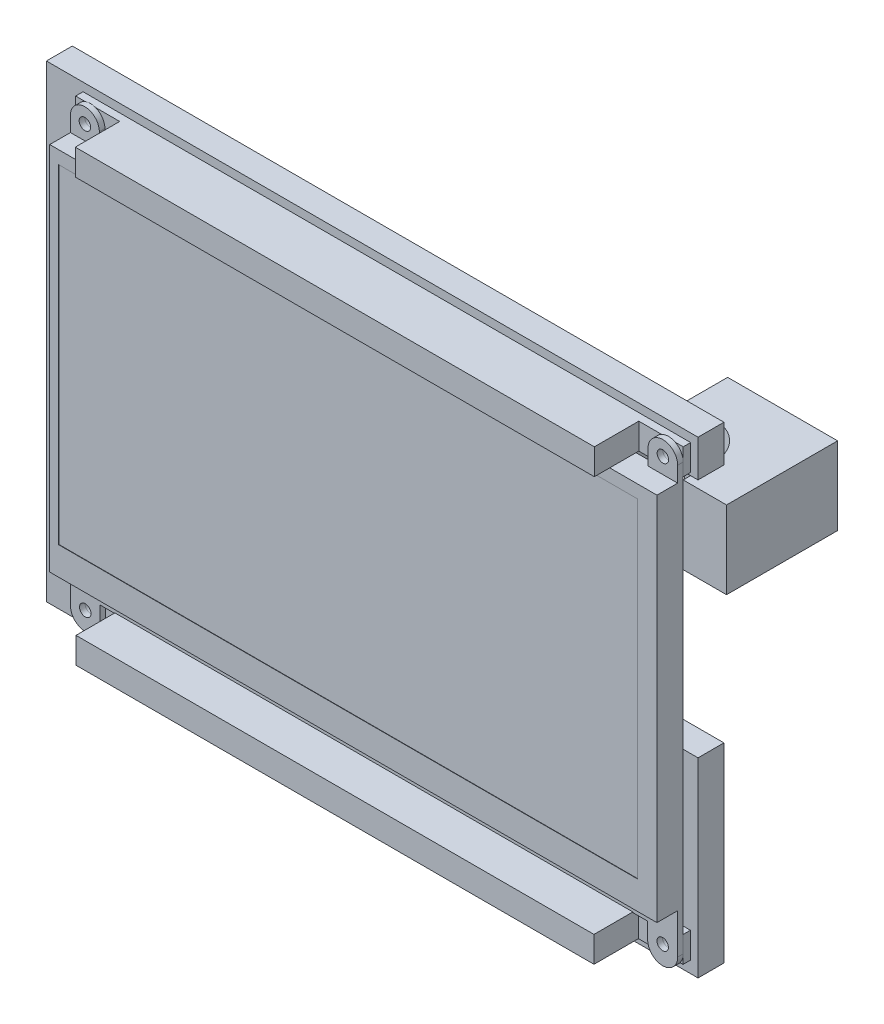
SolidWorks part; units mm, degrees
material "PVC Rigid"
ref_plane "Front Plane" through (0, 0, 0) normal (0, 0, 1) x (1, 0, 0)
ref_plane "Top Plane" through (0, 0, 0) normal (0, 1, 0) x (1, 0, 0)
ref_plane "Right Plane" through (0, 0, 0) normal (1, 0, 0) x (0, 0, -1)
sketch "Sketch1" plane through (0, 0, 0) normal (0, 0, 1) x (1, 0, 0)
  line L1 (-82, -53.25) -> (82, -53.25)
  line L2 (-82, -53.25) -> (-82, 53.25)
  line L3 (-82, 53.25) -> (82, 53.25)
  line L4 (82, -53.25) -> (82, 53.25)
  line L5 (-82, -53.25) -> (82, 53.25) construction
  line L6 (-82, 53.25) -> (82, -53.25) construction
  line L7 (-82, 53.25) -> (-74.2, 53.25)
  line L8 (-82, 53.25) -> (-82, 57.35)
  line L10 (-74.2, 53.25) -> (-74.2, 57.35)
  line L11 (82, 53.25) -> (74, 53.25)
  line L12 (82, 53.25) -> (82, 57.45)
  line L14 (74, 53.25) -> (74, 57.45)
  line L15 (-82, -53.25) -> (-74, -53.25)
  line L16 (-82, -53.25) -> (-82, -57.45)
  line L18 (-74, -53.25) -> (-74, -57.45)
  line L19 (82, -53.25) -> (73.9, -53.25)
  line L20 (82, -53.25) -> (82, -57.6)
  line L22 (73.9, -53.25) -> (73.9, -57.6)
  arc A0 (-74.2, 57.35) -> (-82, 57.35) centre (-78.1, 57.35) ccw
  arc A1 (82, 57.45) -> (74, 57.45) centre (78, 57.45) ccw
  arc A2 (-74, -57.45) -> (-82, -57.45) centre (-78, -57.45) cw
  arc A3 (82, -57.6) -> (73.9, -57.6) centre (77.95, -57.6) cw
  circle A4 centre (77.95, -56.6) radius 1.55
  circle A5 centre (-78, -56.5) radius 1.55
  circle A6 centre (-78.1, 57.2) radius 1.55
  circle A7 centre (78, 57.5) radius 1.55
  point P0 (0, 0)
  point P14 (78, 61.45)
  point P15 (-78.1, 61.25)
  point P24 (-78, -61.45)
  point P25 (77.95, -61.65)
  point P26 (77.1665, -53.25)
  point P29 (77.95, -58.15)
  point P32 (-78.1, 58.75)
  point P37 (-78, -58.05)
  point P38 (78, 59.05)
  dimension "D15" = 3.1
  dimension "D1" = 106.5
  dimension "D2" = 164
  dimension "D3" = 7.8
  dimension "D4" = 8
  dimension "D5" = 8.2
  dimension "D6" = 8
  dimension "D7" = 8.2
  dimension "D8" = 8.4
  dimension "D9" = 3.5
  dimension "D10" = 8.1
  dimension "D11" = 8
  dimension "D12" = 3.4
  dimension "D13" = 2.5
  dimension "D14" = 2.4
extrude "Boss-Extrude1" add sketch "Sketch1" along normal blind 1.5 contours L1 L4 L3 L2 | A2 L18 L1 L16 A5 | A3 L20 L1 L22 A4 | L10 A0 L8 L3 A6 | L12 A1 L14 L3 A7 region at (0, 0, 0) region at (-78, -53.3646, 0) region at (-81.8883, 55.3, 0) region at (77.95, -53.3667, 0) region at (74.1146, 55.35, 0)
sketch "Sketch3" plane through (0, 0, 1.5) normal (0, 0, 1) x (1, 0, 0)
  line L0 (-82, -57.45) -> (-82, 57.35) construction
  line L1 (-82, 53.25) -> (82, 53.25)
  line L2 (-82, 53.25) -> (-82, -46.75)
  line L3 (-82, -46.75) -> (82, -46.75)
  line L4 (82, 53.25) -> (82, -46.75)
  line L5 (82, -57.6) -> (82, 57.45) construction
  line L6 (-74.2, 53.25) -> (74, 53.25) construction
  line L8 (-79.6, 49.75) -> (76.8, 49.75)
  line L9 (-79.6, 49.75) -> (-79.6, -39.15)
  line L10 (-79.6, -39.15) -> (76.8, -39.15)
  line L11 (76.8, 49.75) -> (76.8, -39.15)
  dimension "D1" = 100
  dimension "D2" = 3.5
  dimension "D3" = 2.4
  dimension "D4" = 5.2
  dimension "D5" = 7.6
extrude "Boss-Extrude2" add sketch "Sketch3" along normal blind 7.1 from surface starting at face at (-0.05, -0.0542, 0)
extrude "Boss-Extrude3" add sketch "Sketch3<2>" along normal blind 7 from surface contours L11 L8 L9 L10 region at (-1.4, 5.3, 1.5) starting at face at (-0.05, -0.0542, 0)
sketch "Sketch3<2>" plane through (0, 0, 1.5) normal (0, 0, 1) x (1, 0, 0) same geometry as "Sketch3"
sketch "Sketch4" plane through (0, 0, 0) normal (0, 0, -1) x (-1, 0, 0)
  line L0 (82, -57.45) -> (82, 57.35) construction
  line L1 (-82, 53.25) -> (82, 53.25)
  line L2 (-82, 53.25) -> (-82, -11.75)
  line L3 (-82, -11.75) -> (82, -11.75)
  line L4 (82, 53.25) -> (82, -11.75)
  dimension "D1" = 65
extrude "Boss-Extrude4" add sketch "Sketch4" along normal blind 6
sketch "Sketch5" plane through (0, 0, 0) normal (0, 0, -1) x (-1, 0, 0)
  line L0 (-82, 53.25) -> (-82, -11.75) construction
  line L1 (-82, 53.25) -> (-93.7, 53.25)
  line L2 (-82, 53.25) -> (-82, 32.25)
  line L3 (-82, 32.25) -> (-93.7, 32.25)
  line L4 (-93.7, 53.25) -> (-93.7, 32.25)
  dimension "D1" = 11.7
  dimension "D2" = 21
extrude "Boss-Extrude5" add sketch "Sketch5" along normal blind 30
sketch "Sketch6" plane through (82, 0, 0) normal (-1, 0, 0) x (0, 0, 1)
  line L1 (-30, 53.25) -> (-18.4, 53.25)
  line L2 (-30, 53.25) -> (-30, 32.25)
  line L3 (-30, 32.25) -> (-18.4, 32.25)
  line L4 (-18.4, 53.25) -> (-18.4, 32.25)
  line L6 (0, 53.25) -> (0, 57.35) construction
  line L7 (-30, 32.25) -> (-6, 32.25) construction
  dimension "D1" = 18.4
extrude "Boss-Extrude6" add sketch "Sketch6" along normal blind 18
fillet "Fillet1" radius 10 1 edges at (82, 42.75, -18.4)
sketch "Sketch7" plane through (0, 0, 0) normal (0, 0, -1) x (-1, 0, 0)
  line L0 (82, 53.25) -> (-82, 53.25) construction
  line L1 (-84, 63.25) -> (92, 63.25)
  line L2 (-84, 63.25) -> (-84, 53.25)
  line L3 (-57, 43.25) -> (72, 43.25)
  line L4 (92, 63.25) -> (92, 18.2824)
  line L6 (92, 18.2824) -> (92, -63.25)
  line L8 (72, 43.25) -> (72, -35.25)
  line L9 (92, -63.25) -> (-84, -63.25)
  line L11 (72, -35.25) -> (-72, -35.25)
  line L12 (-84, -63.25) -> (-84, -39.9785)
  line L14 (-84, -39.9785) -> (-84, -11.75)
  line L16 (-72, -35.25) -> (-72, -21.75)
  line L17 (74, -53.25) -> (-73.9, -53.25) construction
  line L18 (82, -11.75) -> (82, 53.25) construction
  line L19 (-82, 32.25) -> (-82, -11.75) construction
  line L20 (-76.8, 49.75) -> (79.6, 49.75) construction
  line L21 (-67, 53.25) -> (-84, 53.25)
  line L22 (-67, 53.25) -> (-67, -11.75)
  line L23 (-67, -11.75) -> (-84, -11.75)
  line L29 (-72, -21.75) -> (-57, -21.75)
  line L30 (-57, 43.25) -> (-57, -21.75)
  line L36 (-76.8, 49.75) -> (79.6, 49.75) construction
  line L37 (-6.1, -42.75) -> (8.9, -42.75) construction
  line L38 (-9.1, -42.75) -> (-6.1, -42.75)
  line L39 (-9.1, -42.75) -> (-9.1, -55.75)
  line L40 (-9.1, -55.75) -> (-6.1, -55.75)
  line L41 (-6.1, -42.75) -> (-6.1, -55.75)
  line L42 (8.9, -42.75) -> (11.9, -42.75)
  line L43 (8.9, -42.75) -> (8.9, -55.75)
  line L44 (8.9, -55.75) -> (11.9, -55.75)
  line L45 (11.9, -42.75) -> (11.9, -55.75)
  line L46 (-82, -57.6) -> (-82, -11.75) construction
  circle A0 centre (78.1, 57.2) radius 1.55 construction
  circle A1 centre (78, -56.5) radius 1.55 construction
  circle A2 centre (-77.95, -56.6) radius 1.55 construction
  circle A3 centre (-78, 57.5) radius 1.55 construction
  circle A4 centre (78.1, 57.2) radius 1.55
  circle A5 centre (78, -56.5) radius 1.55
  circle A6 centre (-77.95, -56.6) radius 1.55
  circle A7 centre (-78, 57.5) radius 1.55
  point P4 (1.4, 49.75)
  point P35 (1.4, -42.75)
  point P37 (11.9, -49.25)
  dimension "D1" = 10
  dimension "D2" = 18
  dimension "D3" = 10
  dimension "D4" = 10
  dimension "D5" = 20
  dimension "D6" = 20
  dimension "D7" = 28
  dimension "D8" = 2
  dimension "D9" = 10
  dimension "D10" = 10
  dimension "D11" = 15
  dimension "D12" = 13
  dimension "D13" = 3
  dimension "D14" = 14
  dimension "D15" = 65
  dimension "D16" = 15
extrude "Boss-Extrude7" add sketch "Sketch7" along normal blind 4 from offset 2 separate body
sketch "Sketch8" plane through (0, 0, -6) normal (0, 0, -1) x (-1, 0, 0)
  line L5 (-82, 53.25) -> (-82, 32.25)
  line L6 (-82, 32.25) -> (-82, -11.75)
  line L7 (-82, -11.75) -> (82, -11.75)
  line L8 (82, -11.75) -> (82, 53.25)
  line L9 (82, 53.25) -> (-82, 53.25)
  line L10 (-82, 53.25) -> (-82, 32.25)
  line L11 (-82, 32.25) -> (-82, -11.75)
  line L12 (-82, -11.75) -> (82, -11.75)
  line L13 (82, -11.75) -> (82, 53.25)
  line L14 (82, 53.25) -> (-82, 53.25)
  dimension "D1" = 0
extrude "Cut-Extrude2" cut sketch "Sketch8" against normal up to surface (6 mm away) up to face at (79.5, -56.6, 0)
sketch "Sketch10" plane through (0, 0, -6) normal (0, 0, -1) x (-1, 0, 0)
  line L0 (-84, -63.25) -> (92, -63.25) construction
  line L1 (-81.1, 63.25) -> (83.9, 63.25)
  line L2 (-81.1, 63.25) -> (-81.1, -63.25)
  line L3 (-81.1, -63.25) -> (83.9, -63.25)
  line L4 (83.9, 63.25) -> (83.9, -63.25)
  line L5 (92, 63.25) -> (-84, 63.25) construction
  line L6 (-76.8, 49.75) -> (79.6, 49.75) construction
  line L7 (-76.8, 49.75) -> (79.6, 49.75) construction
  point P10 (1.4, 63.25)
  point P12 (1.4, 49.75)
  dimension "D1" = 165
sketch "Sketch11" plane through (0, 0, -6) normal (0, 0, -1) x (-1, 0, 0)
  line L0 (92, -63.25) -> (92, 63.25) construction
  line L1 (-84, -38.25) -> (92, -38.25)
  line L2 (-84, -38.25) -> (-84, 5.532)
  line L3 (-84, 5.532) -> (92, 5.532)
  line L4 (92, -38.25) -> (92, 5.532)
  line L5 (-81.1, -63.25) -> (83.9, -63.25) construction
  line L6 (-84, -11.75) -> (-84, -63.25) construction
  line L7 (8.9, -55.75) -> (11.9, -55.75) construction
  line L8 (-67, -11.75) -> (-84, -11.75)
  line L9 (-67, -11.75) -> (-67, 5.532)
  line L10 (-67, 5.532) -> (-84, 5.532)
  line L11 (-84, -11.75) -> (-84, 5.532)
  line L12 (-84, -63.25) -> (92, -63.25)
  line L13 (-84, -63.25) -> (-84, -38.25)
  line L14 (-84, -38.25) -> (92, -38.25)
  line L15 (92, -63.25) -> (92, -38.25)
  line L16 (8.9, -42.75) -> (8.9, -55.75) construction
  line L17 (11.9, -55.75) -> (11.9, -42.75) construction
  line L18 (11.9, -42.75) -> (8.9, -42.75) construction
  line L19 (-6.1, -42.75) -> (-9.1, -42.75) construction
  line L20 (-9.1, -55.75) -> (-6.1, -55.75) construction
  line L21 (-9.1, -42.75) -> (-9.1, -55.75) construction
  line L22 (-6.1, -55.75) -> (-6.1, -42.75) construction
  line L23 (8.9, -55.75) -> (11.9, -55.75)
  line L24 (8.9, -42.75) -> (8.9, -55.75)
  line L25 (11.9, -55.75) -> (11.9, -42.75)
  line L26 (11.9, -42.75) -> (8.9, -42.75)
  line L27 (-6.1, -42.75) -> (-9.1, -42.75)
  line L28 (-9.1, -55.75) -> (-6.1, -55.75)
  line L29 (-9.1, -42.75) -> (-9.1, -55.75)
  line L30 (-6.1, -55.75) -> (-6.1, -42.75)
  line M2 (-9.1, -55.75) -> (-9.1, -42.75)
  line M3 (-9.1, -42.75) -> (-6.1, -42.75)
  line M4 (-6.1, -42.75) -> (-6.1, -55.75)
  line M5 (-6.1, -55.75) -> (-9.1, -55.75)
  line M8 (-67, 53.25) -> (-67, -11.75)
  line M9 (-67, -11.75) -> (-84, -11.75)
  line M10 (-84, -11.75) -> (-84, -63.25)
  line M11 (-84, -63.25) -> (92, -63.25)
  line M12 (92, -63.25) -> (92, 63.25)
  line M14 (72, 43.25) -> (72, -35.25)
  line M15 (72, -35.25) -> (-72, -35.25)
  line M16 (-72, -35.25) -> (-72, -21.75)
  line M17 (-72, -21.75) -> (-57, -21.75)
  line M18 (-57, -21.75) -> (-57, 43.25)
  line M20 (8.9, -55.75) -> (8.9, -42.75)
  line M21 (8.9, -42.75) -> (11.9, -42.75)
  line M22 (11.9, -42.75) -> (11.9, -55.75)
  line M23 (11.9, -55.75) -> (8.9, -55.75)
  circle M25 centre (78, -56.5) radius 1.55
  circle M26 centre (-77.95, -56.6) radius 1.55
  dimension "D1" = 43.782
  dimension "D2" = 25
extrude "Boss-Extrude8" add sketch "Sketch11" along normal blind 3 contours L1 M10 M11 M12 M23 M20 M21 M22 M26 M25 M5 M2 M3 M4 | L3 L1 M8 M9 M10 M12 M14 M15 M16 M17 M18 | L3 M18 M17 M16 M15 M14 region at (82.1864, -25, -6) region at (-4.061, -50.7568, -6) region at (-4.8313, -15.3646, -6)
sketch "Sketch12" plane through (0, 0, -9) normal (0, 0, -1) x (-1, 0, 0)
  line L0 (-67, 5.532) -> (92, 5.532) construction
  line L1 (-36.6, 5.532) -> (39.4, 5.532)
  line L2 (-36.6, 5.532) -> (-36.6, -38.25)
  line L3 (-36.6, -38.25) -> (39.4, -38.25)
  line L4 (39.4, 5.532) -> (39.4, -38.25)
  line L5 (-28.6, 5.532) -> (-28.6, -38.25)
  line L6 (31.4, -38.25) -> (31.4, 5.532)
  line L8 (-28.6, -26.359) -> (-36.6, -26.359)
  line L9 (-28.6, -26.359) -> (-28.6, -6.359)
  line L10 (-28.6, -6.359) -> (-36.6, -6.359)
  line L11 (-36.6, -26.359) -> (-36.6, -6.359)
  line L12 (31.4, -6.359) -> (39.4, -6.359)
  line L13 (31.4, -6.359) -> (31.4, -26.359)
  line L14 (31.4, -26.359) -> (39.4, -26.359)
  line L15 (39.4, -6.359) -> (39.4, -26.359)
  point P4 (1.4, 5.532)
  point P21 (-28.6, -16.359)
  dimension "D1" = 76
  dimension "D2" = 8
  dimension "D3" = 8
  dimension "D4" = 43.782
  dimension "D5" = 20
extrude "Cut-Extrude3" cut sketch "Sketch12" against normal blind 3 contours L5 L10 L2 L8 | L6 L14 L4 L12 region at (32.6, -16.359, -9) region at (-35.4, -16.359, -9)
sketch "Sketch13" plane through (0, 0, -9) normal (0, 0, -1) x (-1, 0, 0)
  line L2 (35.4, -2.359) -> (35.4, -30.359) construction
  line L4 (39.4, -6.359) -> (39.4, -26.359) construction
  line L5 (31.4, -6.359) -> (39.4, -6.359) construction
  circle A0 centre (-32.6, -2.359) radius 2.1
  circle A1 centre (35.4, -2.359) radius 2.1
  circle A2 centre (35.4, -30.359) radius 2.1
  circle A3 centre (-32.6, -30.359) radius 2.1
  point P8 (35.4, -2.6162)
  point P9 (39.4, -16.359)
  point P10 (35.4, -6.359)
  point P12 (-32.6, -2.7013)
  point P17 (35.4, -16.359)
  dimension "D3" = 4.2
  dimension "D1" = 28
  dimension "D2" = 68
extrude "Cut-Extrude4" cut sketch "Sketch13" against normal blind 3
sketch "Sketch14" plane through (0, 0, -2) normal (0, 0, 1) x (1, 0, 0)
  line L0 (-70.2, 61) -> (-70.2, 54)
  line L1 (-82.1, 61) -> (82, 61)
  line L2 (-82.1, 61) -> (-82.1, 54)
  line L3 (-82.1, 54) -> (82, 54)
  line L4 (82, 61) -> (82, 54)
  line L5 (70, 54) -> (70, 61)
  line L6 (-74.2, 53.25) -> (-74.2, 57.35) construction
  line L7 (74, 53.25) -> (74, 57.45) construction
  line L8 (-70, -53.1) -> (-70, -60.1)
  line L9 (-82, -53.1) -> (81.95, -53.1)
  line L10 (-82, -53.1) -> (-82, -60.1)
  line L11 (-82, -60.1) -> (81.95, -60.1)
  line L12 (81.95, -53.1) -> (81.95, -60.1)
  line L13 (69.9, -60.1) -> (69.9, -53.1)
  line L14 (73.9, -53.25) -> (73.9, -57.6) construction
  line L15 (-74, -53.25) -> (-74, -57.45) construction
  point P4 (82, 57.5)
  point P5 (78, 57.5)
  point P6 (-82.1, 57.5)
  point P8 (-78.1, 57.2)
  point P22 (81.95, -56.6)
  point P23 (77.95, -56.6)
  point P24 (-82, -56.6)
  point P25 (-78, -56.5)
  point P30 (-78, -56.5)
  point P31 (77.95, -56.6)
  line M24 (9.1, -42.75) -> (9.1, -55.75)
  line M25 (9.1, -55.75) -> (6.1, -55.75)
  line M26 (6.1, -55.75) -> (6.1, -42.75)
  line M28 (-8.9, -42.75) -> (-8.9, -55.75)
  line M29 (-8.9, -55.75) -> (-11.9, -55.75)
  line M30 (-11.9, -55.75) -> (-11.9, -42.75)
  dimension "D1" = 7
  dimension "D2" = 4
  dimension "D3" = 4
  dimension "D4" = 4
  dimension "D5" = 4
  dimension "D6" = 7
  dimension "D7" = 4
  dimension "D8" = 4
  dimension "D9" = 4
  dimension "D10" = 4
extrude "Boss-Extrude9" add sketch "Sketch14" along normal up to surface (2 mm away) separate body contours L11 L12 L9 L10 | L1 L4 L3 L2 up to face at (-76.55, 57.2, 0)
extrude "Boss-Extrude10" add sketch "Sketch14<3>" along normal offset from surface (14 mm away) 5 contours L3 L5 L1 L0 | L11 L13 L9 L8 M24 M25 M26 M28 M29 M30 | L9 M30 M29 M28 | L9 M26 M25 M24 region at (-0.1, 57.5, -2) region at (-0.0277, -56.6359, -2) region at (-10.4, -54.425, -2) region at (7.6, -54.425, -2) up to face at (-1.4, 5.3, 7) offset beyond the face yes
sketch "Sketch14<3>" plane through (0, 0, -2) normal (0, 0, 1) x (1, 0, 0) same geometry as "Sketch14"
sketch "Sketch15" plane through (0, 0, -9) normal (0, 0, -1) x (-1, 0, 0)
  line L1 (-74.7668, 57.5) -> (-76.3834, 60.3)
  line L2 (-76.3834, 60.3) -> (-79.6166, 60.3)
  line L3 (-79.6166, 60.3) -> (-81.2332, 57.5)
  line L4 (-81.2332, 57.5) -> (-79.6166, 54.7)
  line L5 (-79.6166, 54.7) -> (-76.3834, 54.7)
  line L6 (-76.3834, 54.7) -> (-74.7668, 57.5)
  line L7 (74.8668, 57.2) -> (76.4834, 54.4)
  line L8 (76.4834, 54.4) -> (79.7166, 54.4)
  line L9 (79.7166, 54.4) -> (81.3332, 57.2)
  line L10 (81.3332, 57.2) -> (79.7166, 60)
  line L11 (79.7166, 60) -> (76.4834, 60)
  line L12 (76.4834, 60) -> (74.8668, 57.2)
  line L13 (74.7668, -56.5) -> (76.3834, -59.3)
  line L14 (76.3834, -59.3) -> (79.6166, -59.3)
  line L15 (79.6166, -59.3) -> (81.2332, -56.5)
  line L16 (81.2332, -56.5) -> (79.6166, -53.7)
  line L17 (79.6166, -53.7) -> (76.3834, -53.7)
  line L18 (76.3834, -53.7) -> (74.7668, -56.5)
  line L19 (-74.7168, -56.6) -> (-76.3334, -53.8)
  line L20 (-76.3334, -53.8) -> (-79.5666, -53.8)
  line L21 (-79.5666, -53.8) -> (-81.1832, -56.6)
  line L22 (-81.1832, -56.6) -> (-79.5666, -59.4)
  line L23 (-79.5666, -59.4) -> (-76.3334, -59.4)
  line L24 (-76.3334, -59.4) -> (-74.7168, -56.6)
  circle A0 centre (-78, 57.5) radius 1.55 construction
  circle A1 centre (78, -56.5) radius 1.55 construction
  circle A2 centre (-77.95, -56.6) radius 1.55 construction
  circle A3 centre (78.1, 57.2) radius 1.55 construction
  circle A4 centre (-78, 57.5) radius 1.55 construction
  circle A5 centre (78, -56.5) radius 1.55 construction
  circle A6 centre (-77.95, -56.6) radius 1.55 construction
  circle A7 centre (78.1, 57.2) radius 1.55 construction
  circle A8 centre (-78, 57.5) radius 2.8 construction
  circle A9 centre (78.1, 57.2) radius 2.8 construction
  circle A10 centre (78, -56.5) radius 2.8 construction
  circle A11 centre (-77.95, -56.6) radius 2.8 construction
  circle M21 centre (78, -56.5) radius 1.55
  dimension "D1" = 5.6
extrude "Cut-Extrude5" cut sketch "Sketch15" against normal offset from surface (2.5 mm away) 2.5 contours L17 L18 L13 L14 L15 L16 M21 | L24 L19 L20 L21 L22 L23 region at (-75.6492, -55.1428, -9) up to face at (30.5, -30.359, -9)
extrude "Cut-Extrude6" cut sketch "Sketch15<3>" against normal offset from surface (3.1 mm away) 0.1 contours L1 L2 L3 L4 L5 L6 | L10 L11 L12 L7 L8 L9 up to face at (8.8, 34.1628, -6) offset beyond the face yes
sketch "Sketch15<3>" plane through (0, 0, -9) normal (0, 0, -1) x (-1, 0, 0) same geometry as "Sketch15"
sketch "Sketch16" plane through (0, 0, 1.5) normal (0, 0, 1) x (1, 0, 0)
  circle A0 centre (-78, -56.5) radius 1.55 construction
  circle A1 centre (77.95, -56.6) radius 1.55 construction
  circle A2 centre (78, 57.5) radius 1.55 construction
  circle A3 centre (-78.1, 57.2) radius 1.55 construction
  circle A4 centre (-78, -56.5) radius 1.55
  circle A5 centre (77.95, -56.6) radius 1.55
  circle A6 centre (78, 57.5) radius 1.55
  circle A7 centre (-78.1, 57.2) radius 1.55
extrude "Cut-Extrude7" cut sketch "Sketch16" against normal blind 10
sketch "Sketch17" plane through (0, 0, -6) normal (0, 0, -1) x (-1, 0, 0)
  line L0 (79.7166, 54.4) -> (81.3332, 57.2) construction
  line L1 (81.3332, 57.2) -> (79.7166, 60) construction
  line L2 (79.7166, 60) -> (76.4834, 60) construction
  line L3 (76.4834, 60) -> (74.8668, 57.2) construction
  line L4 (74.8668, 57.2) -> (76.4834, 54.4) construction
  line L5 (76.4834, 54.4) -> (79.7166, 54.4) construction
  line L6 (-76.3834, 54.7) -> (-74.7668, 57.5) construction
  line L7 (-74.7668, 57.5) -> (-76.3834, 60.3) construction
  line L8 (-76.3834, 60.3) -> (-79.6166, 60.3) construction
  line L9 (-79.6166, 60.3) -> (-81.2332, 57.5) construction
  line L10 (-67, 53.25) -> (-67, 5.532)
  line L11 (-67, 5.532) -> (-57, 5.532)
  line L12 (-57, 5.532) -> (-57, 43.25)
  line L13 (-57, 43.25) -> (72, 43.25)
  line L14 (72, 43.25) -> (72, 5.532)
  line L15 (72, 5.532) -> (92, 5.532)
  line L16 (92, 5.532) -> (92, 63.25)
  line L17 (92, 63.25) -> (-84, 63.25)
  line L18 (-84, 63.25) -> (-84, 53.25)
  line L19 (-84, 53.25) -> (-67, 53.25)
  line L20 (-67, 53.25) -> (-67, 5.532)
  line L21 (-67, 5.532) -> (-57, 5.532)
  line L22 (-57, 5.532) -> (-57, 43.25)
  line L23 (-57, 43.25) -> (72, 43.25)
  line L24 (72, 43.25) -> (72, 5.532)
  line L25 (72, 5.532) -> (92, 5.532)
  line L26 (92, 5.532) -> (92, 63.25)
  line L27 (92, 63.25) -> (-84, 63.25)
  line L28 (-84, 63.25) -> (-84, 53.25)
  line L29 (-84, 53.25) -> (-67, 53.25)
  line L30 (-81.2332, 57.5) -> (-79.6166, 54.7) construction
  line L31 (-79.6166, 54.7) -> (-76.3834, 54.7) construction
  line L32 (79.7166, 54.4) -> (81.3332, 57.2)
  line L33 (81.3332, 57.2) -> (79.7166, 60)
  line L34 (79.7166, 60) -> (76.4834, 60)
  line L35 (76.4834, 60) -> (74.8668, 57.2)
  line L36 (74.8668, 57.2) -> (76.4834, 54.4)
  line L37 (76.4834, 54.4) -> (79.7166, 54.4)
  line L38 (-76.3834, 54.7) -> (-74.7668, 57.5)
  line L39 (-74.7668, 57.5) -> (-76.3834, 60.3)
  line L40 (-76.3834, 60.3) -> (-79.6166, 60.3)
  line L41 (-79.6166, 60.3) -> (-81.2332, 57.5)
  line L42 (-81.2332, 57.5) -> (-79.6166, 54.7)
  line L43 (-79.6166, 54.7) -> (-76.3834, 54.7)
  dimension "D1" = 0
extrude "Boss-Extrude12" add sketch "Sketch17" along normal up to surface (3 mm away) up to face at (-78, -56.5, -9)
